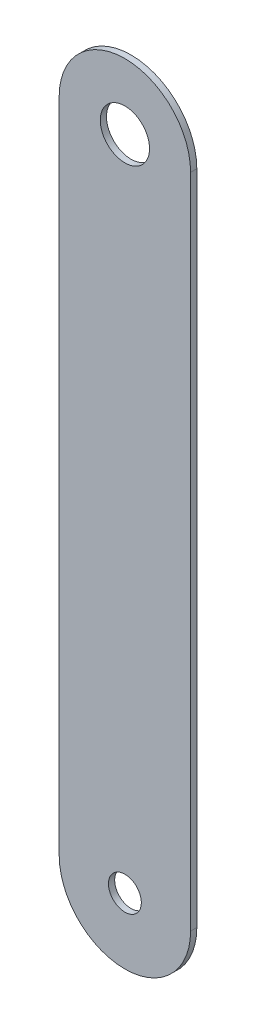
SolidWorks part; units mm, degrees
material "Alloy Steel"
ref_plane "Front" through (0, 0, 0) normal (0, 0, 1) x (1, 0, 0)
ref_plane "Top" through (0, 0, 0) normal (0, 1, 0) x (1, 0, 0)
ref_plane "Right" through (0, 0, 0) normal (1, 0, 0) x (0, 0, -1)
sketch "Sketch1" plane through (0, 0, 0) normal (0, 0, 1) x (1, 0, 0)
  line L1 (-12.7, 63.5) -> (12.7, 63.5)
  line L2 (-12.7, 63.5) -> (-12.7, -63.5)
  line L3 (-12.7, -63.5) -> (12.7, -63.5)
  line L4 (12.7, 63.5) -> (12.7, -63.5)
  line L5 (-12.7, 63.5) -> (12.7, -63.5) construction
  line L6 (-12.7, -63.5) -> (12.7, 63.5) construction
  arc A0 (-12.7, 63.5) -> (12.7, 63.5) centre (0, 63.5) cw
  arc A1 (-12.7, -63.5) -> (12.7, -63.5) centre (0, -63.5) ccw
  circle A2 centre (0, 63.5) radius 4.7625
  circle A3 centre (0, -63.5) radius 3.175
  point P0 (0, 0)
  dimension "D2" = 12.7
  dimension "D4" = 12.7
  dimension "D5" = 9.525
  dimension "D6" = 6.35
  dimension "D1" = 25.4
  dimension "D3" = 127
extrude "Boss-Extrude1" add sketch "Sketch1" along normal blind 1.2 contours A3 L3 L4 L1 A2 L2 | A2 L1 A0 | A3 L3 A1 region at (0, 69.4413, 0) region at (0, -0.38, 0) region at (0, -69.1595, 0)
